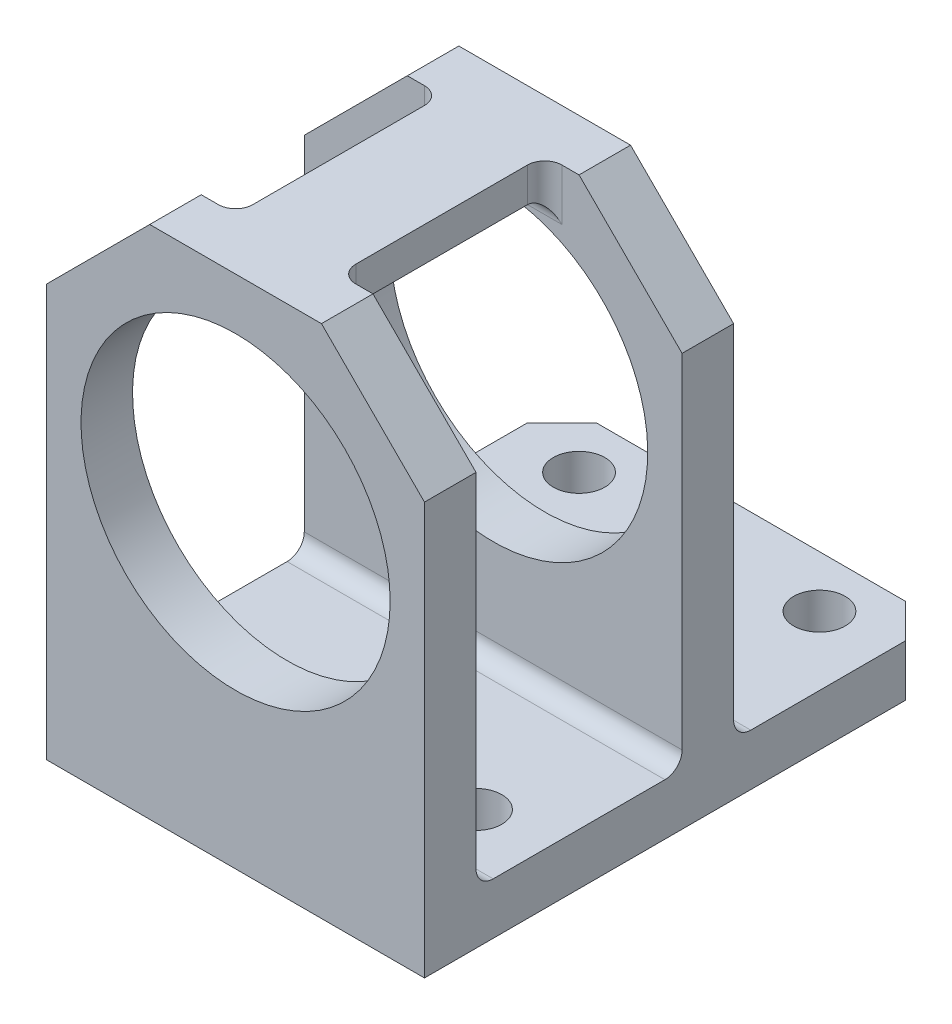
SolidWorks part; units mm, degrees
material "6061-T6 (SS)"
ref_plane "前视基准面" through (0, 0, 0) normal (0, 0, 1) x (1, 0, 0)
ref_plane "上视基准面" through (0, 0, 0) normal (0, 1, 0) x (1, 0, 0)
ref_plane "右视基准面" through (0, 0, 0) normal (1, 0, 0) x (0, 0, -1)
sketch "草图1" plane through (0, 0, 0) normal (0, 0, 1) x (1, 0, 0)
  line L0 (0, 9) -> (0, -9) construction
  line L3 (-11, -18) -> (11, -18)
  line L4 (-11, -18) -> (-11, 12)
  line L5 (-11, 12) -> (11, 12)
  line L6 (11, -18) -> (11, 12)
  line L7 (-11, -18) -> (11, 12) construction
  line L8 (-11, 12) -> (11, -18) construction
  circle A0 centre (0, 0) radius 9
  point P6 (0, -3)
  dimension "D1" = 18
  dimension "D2" = 22
  dimension "D3" = 12
  dimension "D4" = 18
extrude "凸台-拉伸2" add sketch "草图1" along normal blind 30
sketch "草图4" plane through (11, 0, 0) normal (1, 0, 0) x (0, 0, -1)
  line L0 (-30, -18) -> (0, -18) construction
  line L1 (-27, 10) -> (-15, 10)
  line L2 (-27, 10) -> (-27, -15)
  line L3 (-27, -15) -> (-15, -15)
  line L4 (-15, 10) -> (-15, -15)
  line L5 (0, -18) -> (0, 12) construction
  line L6 (-30, -18) -> (-30, 12) construction
  line L7 (-30, 12) -> (0, 12) construction
  line L8 (-12, -15) -> (0, -15)
  line L9 (-12, -15) -> (-12, 15)
  line L10 (-12, 15) -> (0, 15)
  line L11 (0, -15) -> (0, 15)
  dimension "D1" = 3
  dimension "D2" = 12
  dimension "D3" = 3
  dimension "D4" = 3
  dimension "D5" = 2
  dimension "D7" = 30
extrude "切除-拉伸3" cut sketch "草图4" against normal through all
chamfer "倒角2" distance 2 angle 45 2 edges at (-11, -16.5, 0) (11, -16.5, 0)
sketch "草图5" plane through (0, 12, 0) normal (0, 1, 0) x (1, 0, 0)
  line L0 (0, -30) -> (0, -12) construction
  line L1 (11, -30) -> (-11, -30) construction
  line L2 (11, -12) -> (-11, -12) construction
  line L3 (13, -21) -> (9, -21) construction
  line L4 (13, -27) -> (9, -27)
  line L5 (13, -15) -> (9, -15)
  line L6 (11, -30) -> (11, -12) construction
  line L7 (9, -27) -> (3, -27)
  line L8 (3, -27) -> (3, -15)
  line L9 (3, -15) -> (9, -15)
  arc A0 (13, -27) -> (13, -15) centre (13, -21) ccw
  arc A1 (9, -15) -> (9, -27) centre (9, -21) ccw
  point P8 (11, -21)
  point P16 (3, -21)
  line M5 (11, -30) -> (11, -12)
  dimension "D1" = 3
  dimension "D2" = 3
  dimension "D3" = 8
extrude "切除-拉伸4" cut sketch "草图5" against normal up to next contours A1 L8 L7 | L5 A1 L4 M5 | A1 L9 L8 region at (7.5102, 12, 21) region at (4.3402, 12, 25.6598) region at (4.3402, 12, 16.3402)
mirror "镜向1" about plane through (0, 0, 0) normal (1, 0, 0) of "切除-拉伸4"
sketch "草图6" plane through (0, -15, 0) normal (0, 1, 0) x (1, 0, 0)
  line L0 (0, -30) -> (0, 0) construction
  line L1 (11, -30) -> (-11, -30) construction
  line L3 (9, 0) -> (-9, 0) construction
  line L4 (11, -27) -> (11, -15) construction
  circle A0 centre (7, -23) radius 1.5
  circle A1 centre (7, -3) radius 1.5
  circle A2 centre (-7, -3) radius 1.5
  circle A3 centre (-7, -23) radius 1.5
  point P17 (0, 0)
  dimension "D1" = 3
  dimension "D2" = 4
  dimension "D3" = 3
  dimension "D4" = 20
extrude "切除-拉伸5" cut sketch "草图6" against normal through all
chamfer "倒角3" distance 6 angle 45 4 edges at (-11, 12, 13.5) (-11, 12, 28.5) (11, 12, 13.5) (11, 12, 28.5)
fillet "圆角1" radius 1 9 edges at (0, -15, 15) (0, -15, 27) (0, 10, 15) (0, 10, 27) (-3, 11, 27) (-3, 11, 15) (3, 11, 15) (3, 11, 27) (0, -15, 12)
move or copy body "实体-移动/复制1" [suppressed] bodies to move or copy 114
